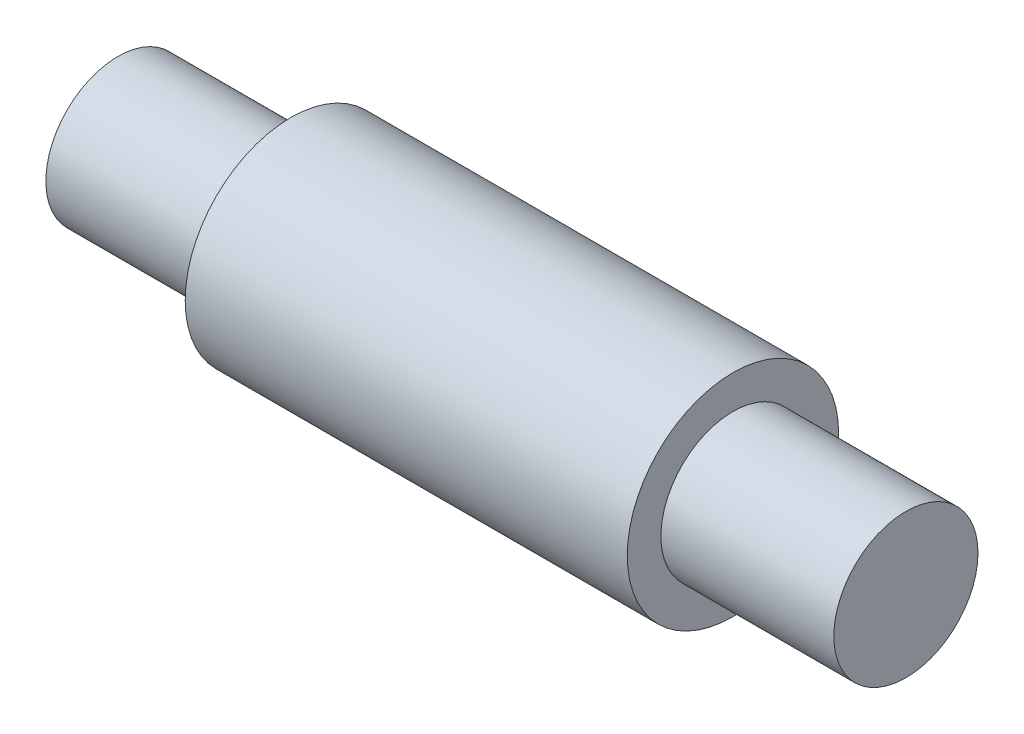
SolidWorks part; units mm, degrees
material "AISI 304"
ref_plane "Plano frontal" through (0, 0, 0) normal (0, 0, 1) x (1, 0, 0)
ref_plane "Plano superior" through (0, 0, 0) normal (0, 1, 0) x (1, 0, 0)
ref_plane "Plano direito" through (0, 0, 0) normal (1, 0, 0) x (0, 0, -1)
sketch "Esboço2" plane through (0, 0, 0) normal (1, 0, 0) x (0, 0, -1)
  circle A0 centre (0, 0) radius 11
  circle A1 centre (0, 0) radius 7.5
  dimension "D1" = 22
  dimension "D2" = 15
extrude "Ressalto-extrusão3" add sketch "Esboço2" along normal mid plane 82 contours A1 region at (0, 0, 0)
cosmetic thread "Representação de rosca2" parameters "D2"=11.797
cosmetic thread "Representação de rosca3" parameters "D2"=11.797
extrude "Ressalto-extrusão4" add sketch "Esboço2<5>" along normal mid plane 46
sketch "Esboço2<5>" plane through (0, 0, 0) normal (1, 0, 0) x (0, 0, -1) same geometry as "Esboço2"
